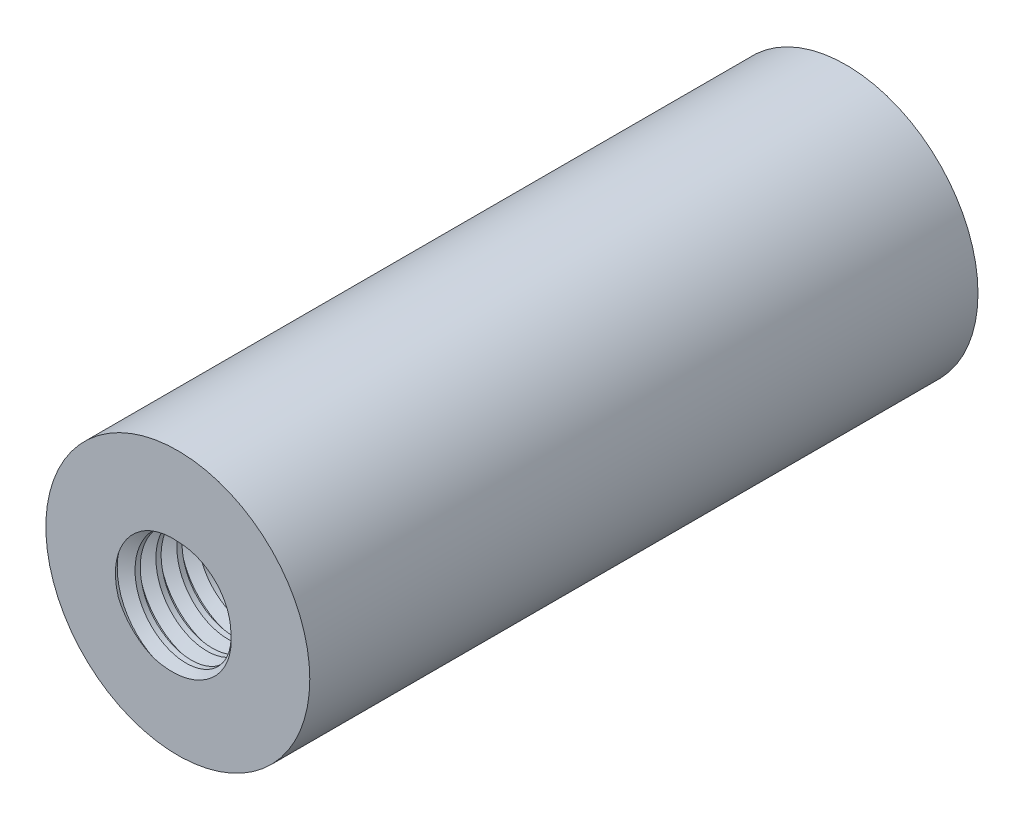
SolidWorks part; units mm, degrees
material "6061-T6 (SS)"
ref_plane "Front Plane" through (0, 0, 0) normal (0, 0, 1) x (1, 0, 0)
ref_plane "Top Plane" through (0, 0, 0) normal (0, 1, 0) x (1, 0, 0)
ref_plane "Right Plane" through (0, 0, 0) normal (1, 0, 0) x (0, 0, -1)
sketch "Sketch1" plane through (0, 0, 0) normal (0, 0, 1) x (1, 0, 0)
  circle A0 centre (0, 0) radius 5.0165
  dimension "D1" = 10.033
extrude "Boss-Extrude1" add sketch "Sketch1" along normal blind 25.4
sketch "Sketch2" plane through (0, 0, 0) normal (0, 0, -1) x (-1, 0, 0)
  circle A0 centre (0, 0) radius 2.0193
  dimension "D1" = 4.0386
extrude "Cut-Extrude1" cut sketch "Sketch2" against normal through all contours A0
thread "Thread1" pitch 0.7937 profile "Thread Profile1" start angle 0, offset 0, length 0, pitch 0.7937, diameter 4.0386
ref_plane "Plane1" through (2.0193, 0, 0) normal (0, -1, 0) x (1, 0, 0)
sketch "Thread Profile1" plane through (2.0193, 0, 0) normal (0, -1, 0) x (1, 0, 0)
  line L0 (0, 0) -> (0, 0.7937) construction
  line L1 (0, 0) -> (0.4296, 0.248)
  line L2 (0.4296, 0.248) -> (0.4296, 0.3473)
  line L3 (0.4296, 0.3473) -> (0, 0.5953)
  line L4 (0.4296, 0.2977) -> (0, 0.2977) construction
  line L11 (0, 0) -> (0, 0.5953)
  point P2 (0, 0)
  dimension "Pitch" = 0.7937
  dimension "Profile_Angle" = 60
  dimension "Profile_Land" = 0.0992
  dimension "Profile_Height" = 0.4296
